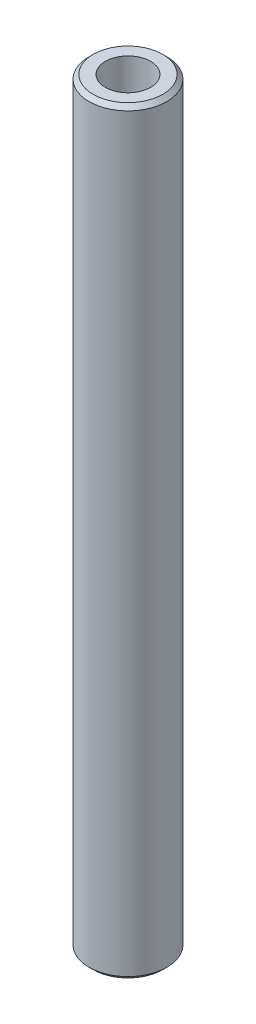
SolidWorks part; units mm, degrees
ref_plane "Front Plane" through (0, 0, 0) normal (0, 0, 1) x (1, 0, 0)
ref_plane "Top Plane" through (0, 0, 0) normal (0, 1, 0) x (1, 0, 0)
ref_plane "Right Plane" through (0, 0, 0) normal (1, 0, 0) x (0, 0, -1)
sketch "Sketch1" plane through (0, 0, 0) normal (0, 1, 0) x (1, 0, 0)
  circle A0 centre (0, 0) radius 10
  dimension "SHAFT_OD" = 20
extrude "Boss-Extrude1" add sketch "Sketch1" along normal blind 194.944
sketch "Sketch2" plane through (0, 0, 0) normal (0, 1, 0) x (1, 0, 0)
  circle A0 centre (0, 0) radius 5.8136
  dimension "BORE_D" = 11.6271
extrude "Cut-Extrude1" cut sketch "Sketch2" along normal through all
chamfer "Chamfer1" distance 1.0717 angle 45 2 edges at (0, 194.944, 10) (0, 0, 10)
